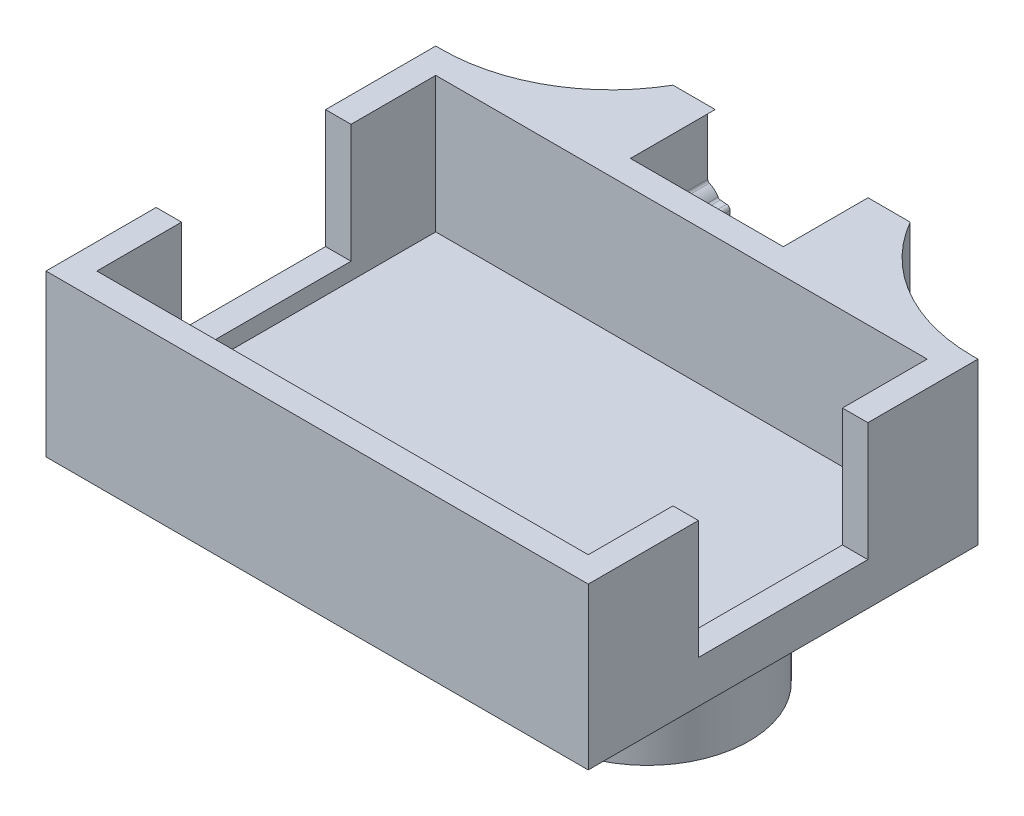
SolidWorks part; units mm, degrees
ref_plane "Front Plane" through (0, 0, 0) normal (0, 0, 1) x (1, 0, 0)
ref_plane "Top Plane" through (0, 0, 0) normal (0, 1, 0) x (1, 0, 0)
ref_plane "Right Plane" through (0, 0, 0) normal (1, 0, 0) x (0, 0, -1)
sketch "Sketch4" plane through (0, 0, 0) normal (0, 1, 0) x (1, 0, 0)
  line L1 (-16, -11.5) -> (16, -11.5)
  line L2 (-16, -11.5) -> (-16, 11.5)
  line L3 (-16, 11.5) -> (16, 11.5)
  line L4 (16, -11.5) -> (16, 11.5)
  line L5 (-16, -11.5) -> (16, 11.5) construction
  line L6 (-16, 11.5) -> (16, -11.5) construction
  point P0 (0, 0)
  dimension "D1" = 32
  dimension "D2" = 23
extrude "Boss-Extrude3" add sketch "Sketch4" along normal blind 9.5
sketch "Sketch5" plane through (0, 9.5, 0) normal (0, 1, 0) x (1, 0, 0)
  line L1 (-14.5, -10) -> (14.5, -10)
  line L2 (-14.5, -10) -> (-14.5, 10)
  line L3 (-14.5, 10) -> (14.5, 10)
  line L4 (14.5, -10) -> (14.5, 10)
  line L5 (-14.5, -10) -> (14.5, 10) construction
  line L6 (-14.5, 10) -> (14.5, -10) construction
  point P0 (0, 0)
  dimension "D1" = 29
  dimension "D2" = 20
extrude "Cut-Extrude2" cut sketch "Sketch5" against normal blind 8
sketch "Sketch8" plane through (-16, 0, 0) normal (-1, 0, 0) x (0, 0, 1)
  line L2 (-11.5, 9.5) -> (11.5, 9.5) construction
  line L4 (11.5, 9.5) -> (11.5, 0) construction
  line L8 (-2.2, 9.5) -> (-1.4, 9.5)
  spline S0 degree 3 poles (-2.2, 9.5) (-2.1353, 9.2413) (-1.5778, 9.0675) (-1.4, 9.5) knots 0 0 0 0 1 1 1 1
  line B0 (4.5, 6.0583) -> (4.5, 9.1)
  line B1 (4.5, 9.1) -> (4.1, 9.5)
  line B2 (4.1, 9.5) -> (-1.4, 9.5)
  line B3 (-2.2, 9.5) -> (-4.1, 9.5)
  line B4 (-4.1, 9.5) -> (-4.5, 9.1)
  line B5 (-4.5, 9.1) -> (-4.5, 6.0583)
  line B6 (-3.8235, 5.4365) -> (-3.4826, 5.4066)
  line B7 (-3.3, 5.2074) -> (-3.3, 4.7926)
  line B8 (-3.4826, 4.5934) -> (-3.8235, 4.5635)
  line B9 (-4.5, 3.9417) -> (-4.5, 3.4)
  line B10 (-4.5, 3.4) -> (-4.1, 3)
  line B11 (-4.1, 3) -> (4.1, 3)
  line B12 (4.1, 3) -> (4.5, 3.4)
  line B13 (4.5, 3.4) -> (4.5, 3.9417)
  line B14 (3.8235, 4.5635) -> (3.4826, 4.5934)
  line B15 (3.3, 4.7926) -> (3.3, 5.2074)
  line B16 (3.4826, 5.4066) -> (3.8235, 5.4365)
  arc B17 (-2.2, 9.5) -> (-1.4, 9.5) centre (-1.8, 9.8) ccw
  arc B18 (-4.5, 6.0583) -> (-4.4087, 5.9203) centre (-4.35, 6.0583) ccw
  arc B19 (-3.9395, 5.5095) -> (-4.4087, 5.9203) centre (-4.8, 5) ccw
  arc B20 (-3.9395, 5.5095) -> (-3.8235, 5.4365) centre (-3.8104, 5.5859) ccw
  arc B21 (-3.3, 5.2074) -> (-3.4826, 5.4066) centre (-3.5, 5.2074) ccw
  arc B22 (-3.4826, 4.5934) -> (-3.3, 4.7926) centre (-3.5, 4.7926) ccw
  arc B23 (-3.8235, 4.5635) -> (-3.9395, 4.4905) centre (-3.8104, 4.4141) ccw
  arc B24 (-4.4087, 4.0797) -> (-3.9395, 4.4905) centre (-4.8, 5) ccw
  arc B25 (-4.4087, 4.0797) -> (-4.5, 3.9417) centre (-4.35, 3.9417) ccw
  arc B26 (4.5, 3.9417) -> (4.4087, 4.0797) centre (4.35, 3.9417) ccw
  arc B27 (3.9395, 4.4905) -> (4.4087, 4.0797) centre (4.8, 5) ccw
  arc B28 (3.9395, 4.4905) -> (3.8235, 4.5635) centre (3.8104, 4.4141) ccw
  arc B29 (3.3, 4.7926) -> (3.4826, 4.5934) centre (3.5, 4.7926) ccw
  arc B30 (3.4826, 5.4066) -> (3.3, 5.2074) centre (3.5, 5.2074) ccw
  arc B31 (3.8235, 5.4365) -> (3.9395, 5.5095) centre (3.8104, 5.5859) ccw
  arc B32 (4.4087, 5.9203) -> (3.9395, 5.5095) centre (4.8, 5) ccw
  arc B33 (4.4087, 5.9203) -> (4.5, 6.0583) centre (4.35, 6.0583) ccw
  line M194 (11.5, 9.5) -> (-11.5, 9.5)
  dimension "D1" = 7
sketch_block_instance "9mm Block-2"
sketch_block "9mm Block"
extrude "Cut-Extrude4" cut sketch "Sketch8" against normal up to surface (32 mm away) contours B32 B33 B0 B1 S0 B4 B5 B18 B19 B20 B6 B21 B7 B22 B8 B23 B24 B25 B9 B10 B11 B12 B13 B26 B27 B28 B14 B29 B15 B30 B16 B31 M194 | B17 M194 | B17 S0 region at (-16, 9.2916, -1.8) region at (-16, 6.3052, 0.005) region at (-16, 9.4184, -1.8) up to face at (16, 4.75, 0)
sketch "Sketch9" plane through (0, 0, 0) normal (0, -1, 0) x (-1, 0, 0)
  line L0 (16, -11.5) -> (-16, -11.5) construction
  line L1 (0, -11.5) -> (0, 11.5) construction
  line L2 (-16, 11.5) -> (16, 11.5) construction
  line L3 (0, -11.5) -> (16, 11.5) construction
  line L4 (16, -11.5) -> (0, 11.5) construction
  circle A0 centre (8, 0) radius 4.8125
  circle A1 centre (8, 0) radius 6
  circle A2 centre (-8, 0) radius 4.8125
  circle A3 centre (-8, 0) radius 6
  dimension "D1" = 9.625
  dimension "D2" = 12
extrude "Boss-Extrude5" add sketch "Sketch9" along normal blind 3.275 contours A1 | A3 | A2 | A0
sketch "Sketch10" plane through (0, -3.275, 0) normal (0, -1, 0) x (-1, 0, 0)
  line L0 (0, -11.5) -> (0, 11.5) construction
  line L1 (16, -11.5) -> (-16, -11.5) construction
  line L2 (-16, 11.5) -> (16, 11.5) construction
  circle A0 centre (8, 0) radius 6
  circle A1 centre (8, 0) radius 3.6
  circle A2 centre (-8, 0) radius 3.6
  circle A3 centre (-8, 0) radius 6
  dimension "D1" = 12
  dimension "D2" = 7.2
extrude "Boss-Extrude6" add sketch "Sketch10" along normal blind 2
sketch "Sketch12" plane through (-16, 0, 0) normal (-1, 0, 0) x (0, 0, 1)
  line L0 (4.1, 9.5) -> (11.5, 9.5) construction
  line L5 (-5, 2.5) -> (5, 2.5)
  line L6 (-5, 2.5) -> (-5, 9.5)
  line L7 (-5, 9.5) -> (5, 9.5)
  line L8 (5, 2.5) -> (5, 9.5)
  line L9 (-5, 2.5) -> (5, 9.5) construction
  line L10 (-5, 9.5) -> (5, 2.5) construction
  line L11 (11.5, 9.5) -> (11.5, 0) construction
  point P4 (0, 6)
  dimension "D1" = 10
  dimension "D2" = 7
  dimension "D3" = 6.5
extrude "Cut-Extrude5" cut sketch "Sketch12" against normal up to surface (32 mm away) up to face at (16, 5.25, 0)
sketch "Sketch15" plane through (0, 0, -11.5) normal (0, 0, -1) x (-1, 0, 0)
  line L0 (-16, 9.5) -> (16, 9.5) construction
  line L1 (-16, 0) -> (16, 0) construction
  line L2 (16, 9.5) -> (16, 0) construction
  line L3 (-7, 9.5) -> (7, 9.5)
  line L4 (-7, 9.5) -> (-7, 0)
  line L5 (-7, 0) -> (7, 0)
  line L6 (7, 9.5) -> (7, 0)
  line L7 (-7, 9.5) -> (7, 0) construction
  line L8 (-7, 0) -> (7, 9.5) construction
  point P8 (0, 2.35)
  point P14 (0, 4.75)
  line B0 (4.95, 5.7141) -> (4.95, 9.06)
  line B1 (4.95, 9.06) -> (4.51, 9.5)
  line B2 (4.51, 9.5) -> (-1.54, 9.5)
  line B3 (-2.42, 9.5) -> (-4.51, 9.5)
  line B4 (-4.51, 9.5) -> (-4.95, 9.06)
  line B5 (-4.95, 9.06) -> (-4.95, 5.7141)
  line B6 (-4.2059, 5.0301) -> (-3.8308, 4.9973)
  line B7 (-3.63, 4.7781) -> (-3.63, 4.3219)
  line B8 (-3.8308, 4.1027) -> (-4.2059, 4.0699)
  line B9 (-4.95, 3.3859) -> (-4.95, 2.79)
  line B10 (-4.95, 2.79) -> (-4.51, 2.35)
  line B11 (-4.51, 2.35) -> (4.51, 2.35)
  line B12 (4.51, 2.35) -> (4.95, 2.79)
  line B13 (4.95, 2.79) -> (4.95, 3.3859)
  line B14 (4.2059, 4.0699) -> (3.8308, 4.1027)
  line B15 (3.63, 4.3219) -> (3.63, 4.7781)
  line B16 (3.8308, 4.9973) -> (4.2059, 5.0301)
  arc B17 (-2.42, 9.5) -> (-1.54, 9.5) centre (-1.98, 9.83) ccw
  arc B18 (-4.95, 5.7141) -> (-4.8496, 5.5623) centre (-4.785, 5.7141) ccw
  arc B19 (-4.3335, 5.1104) -> (-4.8496, 5.5623) centre (-5.28, 4.55) ccw
  arc B20 (-4.3335, 5.1104) -> (-4.2059, 5.0301) centre (-4.1915, 5.1945) ccw
  arc B21 (-3.63, 4.7781) -> (-3.8308, 4.9973) centre (-3.85, 4.7781) ccw
  arc B22 (-3.8308, 4.1027) -> (-3.63, 4.3219) centre (-3.85, 4.3219) ccw
  arc B23 (-4.2059, 4.0699) -> (-4.3335, 3.9896) centre (-4.1915, 3.9055) ccw
  arc B24 (-4.8496, 3.5377) -> (-4.3335, 3.9896) centre (-5.28, 4.55) ccw
  arc B25 (-4.8496, 3.5377) -> (-4.95, 3.3859) centre (-4.785, 3.3859) ccw
  arc B26 (4.95, 3.3859) -> (4.8496, 3.5377) centre (4.785, 3.3859) ccw
  arc B27 (4.3335, 3.9896) -> (4.8496, 3.5377) centre (5.28, 4.55) ccw
  arc B28 (4.3335, 3.9896) -> (4.2059, 4.0699) centre (4.1915, 3.9055) ccw
  arc B29 (3.63, 4.3219) -> (3.8308, 4.1027) centre (3.85, 4.3219) ccw
  arc B30 (3.8308, 4.9973) -> (3.63, 4.7781) centre (3.85, 4.7781) ccw
  arc B31 (4.2059, 5.0301) -> (4.3335, 5.1104) centre (4.1915, 5.1945) ccw
  arc B32 (4.8496, 5.5623) -> (4.3335, 5.1104) centre (5.28, 4.55) ccw
  arc B33 (4.8496, 5.5623) -> (4.95, 5.7141) centre (4.785, 5.7141) ccw
  line M2 (-16, 0) -> (16, 0)
  line M4 (16, 9.5) -> (-16, 9.5)
  dimension "D1" = 14
  dimension "D2" = 9
sketch_block_instance "9mm Block-7"
extrude "Boss-Extrude7" add sketch "Sketch15" along normal blind 5 contours B33 B32 B31 B16 B30 B15 B29 B14 B28 B27 B26 B13 B12 B11 B10 B9 B25 B24 B23 B8 B22 B7 B21 B6 B20 B19 B18 B5 B4 L4 L6 B1 B0 M4 M2 region at (5.755, 9.3308, -11.5)
fillet "Fillet1" radius 10 2 edges at (-7, 4.75, -11.5) (7, 4.75, -11.5)
